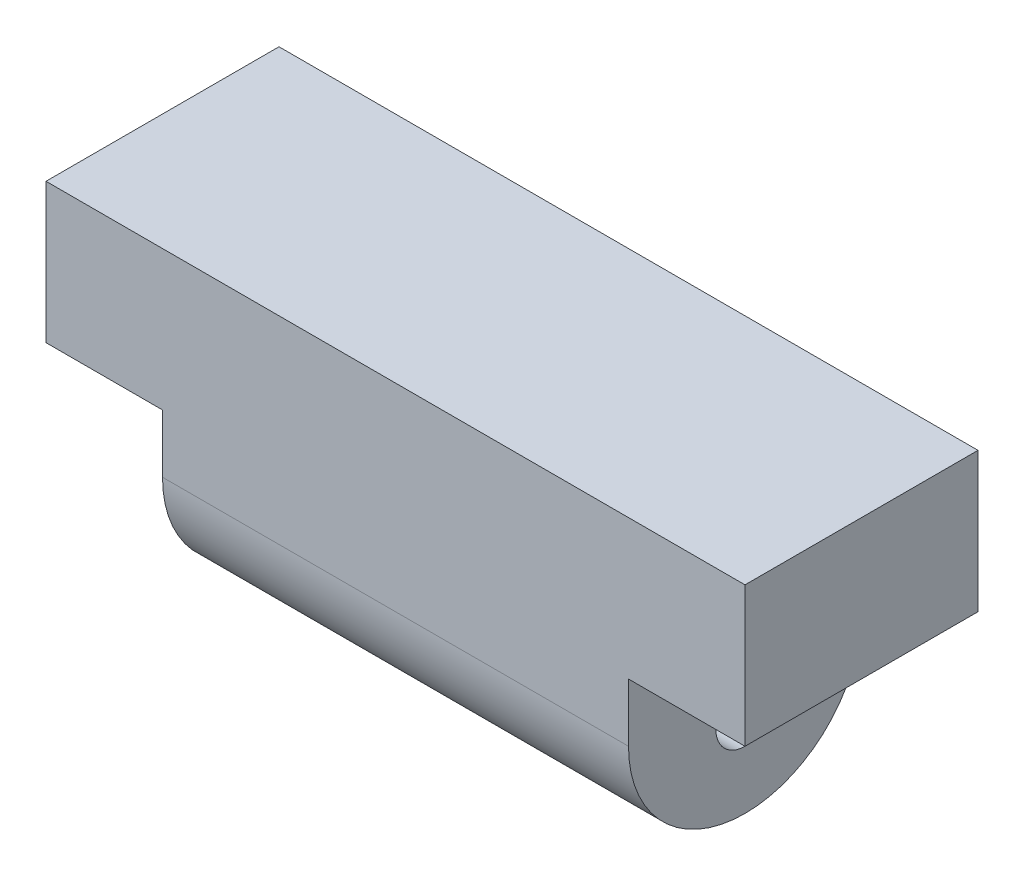
SolidWorks part; units mm, degrees
ref_plane "Front Plane" through (0, 0, 0) normal (0, 0, 1) x (1, 0, 0)
ref_plane "Top Plane" through (0, 0, 0) normal (0, 1, 0) x (1, 0, 0)
ref_plane "Right Plane" through (0, 0, 0) normal (1, 0, 0) x (0, 0, -1)
sketch "Sketch1" plane through (0, 0, 0) normal (0, 0, 1) x (1, 0, 0)
  line L0 (-30, 13.5) -> (30, 13.5)
  line L1 (30, 13.5) -> (30, 1.5)
  line L2 (30, 1.5) -> (20, 1.5)
  line L3 (20, 1.5) -> (20, -13.5)
  line L4 (20, -13.5) -> (-20, -13.5)
  line L5 (-20, -13.5) -> (-20, 1.5)
  line L6 (-20, 1.5) -> (-30, 1.5)
  line L7 (-30, 1.5) -> (-30, 13.5)
  dimension "D1" = 15
  dimension "D2" = 15
  dimension "D3" = 40
  dimension "D4" = 10
  dimension "D5" = 10
  dimension "D6" = 12
  dimension "D7" = 20
  dimension "D8" = 13.5
extrude "Boss-Extrude1" add sketch "Sketch1" along normal blind 20
sketch "Sketch2" plane through (20, 0, 0) normal (1, 0, 0) x (0, 0, -1)
  line L0 (0, -13.5) -> (0, 1.5) construction
  line L1 (-20, -13.5) -> (0, -13.5) construction
  circle A0 centre (-10, -6) radius 2.5
  point P2 (0, -6)
  point P7 (-11.1336, -10.3586)
  dimension "D1" = 5
  dimension "D2" = 10
  dimension "D3" = 7.5
extrude "Cut-Extrude1" cut sketch "Sketch2" against normal through all
fillet "Fillet1" radius 10 2 edges at (0, -13.5, 0) (0, -13.5, 20)
